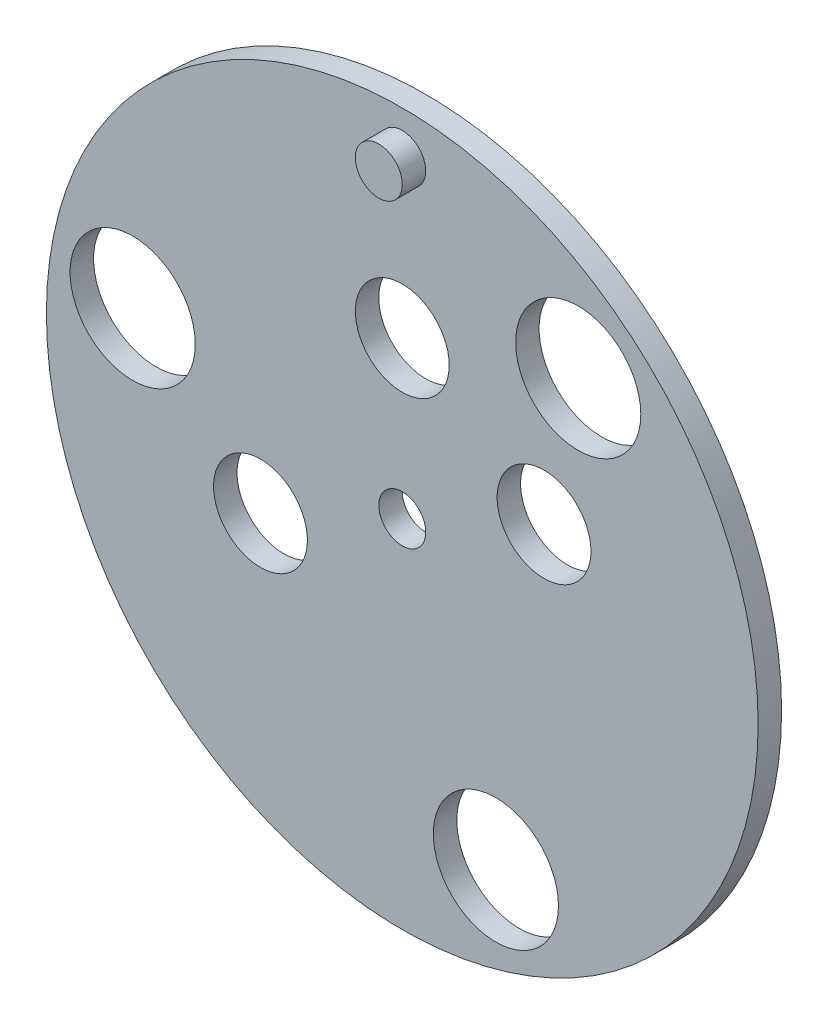
SolidWorks part; units mm, degrees
ref_plane "Front Plane" through (0, 0, 0) normal (0, 0, 1) x (1, 0, 0)
ref_plane "Top Plane" through (0, 0, 0) normal (0, 1, 0) x (1, 0, 0)
ref_plane "Right Plane" through (0, 0, 0) normal (1, 0, 0) x (0, 0, -1)
sketch "Sketch1" plane through (0, 0, 0) normal (0, 0, 1) x (1, 0, 0)
  circle A0 centre (0, 0) radius 227.5
  circle A1 centre (0, 200) radius 15
  dimension "D2" = 30
  dimension "D3" = 455
  dimension "D1" = 200
extrude "Boss-Extrude1" add sketch "Sketch1" along normal mid plane 15 contours A0
extrude "Boss-Extrude2" add sketch "Sketch1<3>" along normal blind 15 from surface contours A1 region at (0, 200, 0) starting at face at (227.5, 0, 7.5)
sketch "Sketch1<3>" plane through (0, 0, 0) normal (0, 0, 1) x (1, 0, 0) same geometry as "Sketch1"
sketch "Sketch2" plane through (0, 0, 7.5) normal (0, 0, 1) x (1, 0, 0)
  line L0 (90.6308, 42.2618) -> (-90.6308, -42.2618) construction
  line L1 (0, -100) -> (0, 100) construction
  line L2 (-172.3414, 30.3884) -> (0, 0) construction
  line L3 (59.8535, -164.4462) -> (0, 0) construction
  line L4 (0, 0) -> (112.4878, 134.0578) construction
  circle A0 centre (-172.3414, 30.3884) radius 40
  circle A2 centre (0, 100) radius 30
  circle A4 centre (90.6308, 42.2618) radius 30
  circle A9 centre (-90.6308, -42.2618) radius 30
  circle A10 centre (112.4878, 134.0578) radius 40
  circle A11 centre (59.8535, -164.4462) radius 40
  dimension "D1" = 60
  dimension "D4" = 100
  dimension "D8" = 60
  dimension "D11" = 3
  dimension "D12" = 120
  dimension "D7" = 80
  dimension "D2" = 100
  dimension "D6" = 175
  dimension "D3" = 100
  dimension "D9" = 115
  dimension "D10" = 80
  dimension "D13" = 120
extrude "Cut-Extrude1" cut sketch "Sketch2" against normal through all
sketch "Sketch3" plane through (0, 0, 0) normal (0, 0, 1) x (1, 0, 0)
  circle A0 centre (0, 0) radius 15
  dimension "D1" = 30
extrude "Cut-Extrude3" cut sketch "Sketch3" against normal up to surface (7.5 mm away) from surface contours A0 up to face at (-132.3414, 30.3884, -7.5) starting at face at (-132.3414, 30.3884, 7.5)
